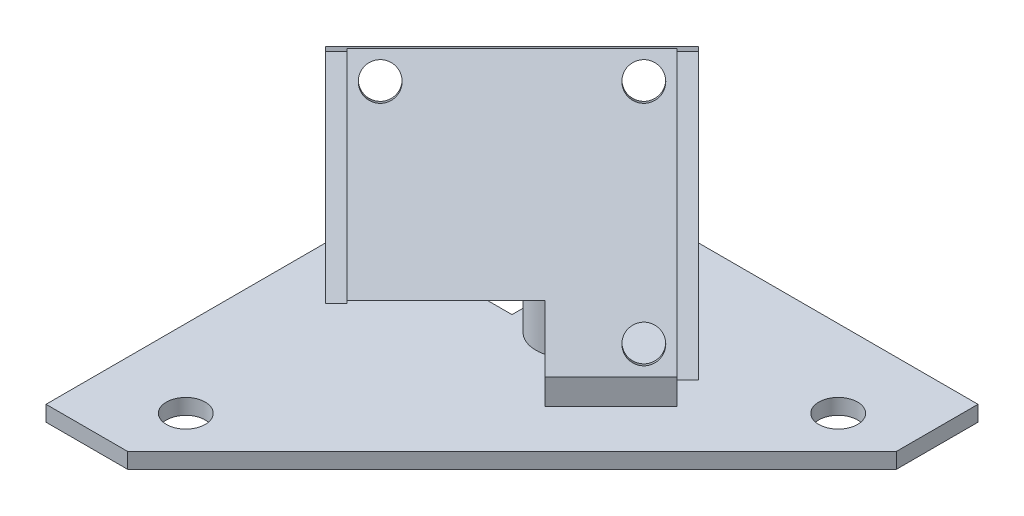
SolidWorks part; units mm, degrees
ref_plane "Front" through (0, 0, 0) normal (0, 0, 1) x (1, 0, 0)
ref_plane "Top" through (0, 0, 0) normal (0, 1, 0) x (1, 0, 0)
ref_plane "Right" through (0, 0, 0) normal (1, 0, 0) x (0, 0, -1)
sketch "草图1" plane through (0, 0, 0) normal (0, 1, 0) x (1, 0, 0)
  line L0 (87.1745, 16.672) -> (1.4976, -69.0049)
  line L1 (0, 0) -> (60, 0)
  line L2 (0, 0) -> (0, -60)
  line L3 (0, -60) -> (60, -60)
  line L4 (60, 0) -> (60, -60)
  line L5 (0, 0) -> (20, 0)
  line L6 (0, 0) -> (0, -20)
  line L7 (0, -20) -> (20, -20)
  line L8 (20, 0) -> (20, -20)
  circle A0 centre (10, -52) radius 2.5
  circle A1 centre (52, -10) radius 2.5
  dimension "D5" = 5
  dimension "D8" = 5
  dimension "D1" = 60
  dimension "D2" = 60
  dimension "D3" = 20
  dimension "D4" = 20
  dimension "D6" = 10
  dimension "D7" = 8
  dimension "D9" = 10
  dimension "D10" = 8
  dimension "D11" = 35
extrude "凸台-拉伸1" add sketch "草图1" along normal blind 2 contours L1 L8 L7 L2 L3 L4 region at (25.5687, 0, 25.5687)
ref_plane "基准面1" through (23.1124, 18.8712, 23.1124) normal (0.6124, 0.5, 0.6124) x (-0.7071, 0, 0.7071)
sketch "草图2" plane through (23.1124, 18.8712, 23.1124) normal (0.6124, 0.5, 0.6124) x (-0.7071, 0, 0.7071)
  line L0 (20.7547, -10.214) -> (-21.3736, -10.214) construction
  line L1 (-15, 16.786) -> (15, 16.786)
  line L2 (-15, 16.786) -> (-15, -13.214)
  line L3 (-15, -13.214) -> (15, -13.214)
  line L4 (15, 16.786) -> (15, -13.214)
  line L5 (-15, 16.786) -> (15, -13.214) construction
  line L6 (-15, -13.214) -> (15, 16.786) construction
  line L7 (0, -2.8326) -> (0, 36.0846) construction
  line L8 (27.4605, 1.786) -> (-33.4746, 1.786) construction
  line L10 (15, 16.786) -> (-3, 16.786)
  line L11 (15, 16.786) -> (15, 9.786)
  line L12 (15, 9.786) -> (-3, 9.786)
  line L13 (-3, 16.786) -> (-3, 9.786)
  circle A0 centre (12, -10.214) radius 2
  circle A1 centre (-12, -10.214) radius 2
  circle A2 centre (-12, 13.786) radius 2
  circle A3 centre (12, 13.786) radius 2
  point P0 (0, 1.786)
  dimension "D4" = 4
  dimension "D1" = 30
  dimension "D2" = 30
  dimension "D3" = 12
  dimension "D5" = 12
  dimension "D6" = 7
  dimension "D7" = 18
extrude "凸台-拉伸3" add sketch "草图2" along normal blind 2 separate body contours L13 L1 L2 L3 L4 L12 A2 A0 A1 region at (23.7017, 18.8514, 22.5393)
sketch "草图4" plane through (0, 2, 0) normal (0, 1, 0) x (1, 0, 0)
  line L12 (28.6936, -38.5931) -> (31.1685, -41.0679)
  line L13 (15.9657, -51.321) -> (28.6936, -38.5931)
  line L14 (-6.3082, -29.0471) -> (15.9657, -51.321)
  line L15 (29.0471, 6.3082) -> (-6.3082, -29.0471)
  line L16 (53.7959, -18.4405) -> (29.0471, 6.3082)
  line L17 (31.1685, -41.0679) -> (53.7959, -18.4405)
  line L18 (28.6936, -38.5931) -> (31.1685, -41.0679)
  line L19 (15.9657, -51.321) -> (28.6936, -38.5931)
  line L20 (-6.3082, -29.0471) -> (15.9657, -51.321)
  line L21 (29.0471, 6.3082) -> (-6.3082, -29.0471)
  line L22 (53.7959, -18.4405) -> (29.0471, 6.3082)
  line L23 (31.1685, -41.0679) -> (53.7959, -18.4405)
  circle A0 centre (25.5116, -18.4405) radius 4
  dimension "D2" = 8
  dimension "D3" = 15
  dimension "D4" = 20
  dimension "D1" = 10
extrude "凸台-拉伸4" add sketch "草图4" along normal up to surface (14.7556 mm away) contours A0 region at (25.5116, 2, 18.4405) up to face at (37.886, 6.9321, 18.087)
sketch "草图5" plane through (0, 2, 0) normal (0, 1, 0) x (1, 0, 0)
  line L4 (39.6537, -18.4405) -> (31.1685, -26.9258)
  line L5 (40.8785, -19.6653) -> (39.6537, -18.4405)
  line L6 (32.3932, -28.1506) -> (40.8785, -19.6653)
  line L7 (60, 0) -> (20, 0)
  line L8 (20, 0) -> (20, -20)
  line L9 (20, -20) -> (0, -20)
  line L10 (0, -20) -> (0, -60)
  line L11 (0, -60) -> (10.5025, -60)
  line L12 (10.5025, -60) -> (60, -10.5025)
  line L13 (60, -10.5025) -> (60, 0)
  line L14 (60, 0) -> (20, 0)
  line L15 (20, 0) -> (20, -20)
  line L16 (20, -20) -> (0, -20)
  line L17 (0, -20) -> (0, -60)
  line L18 (0, -60) -> (10.5025, -60)
  line L19 (10.5025, -60) -> (60, -10.5025)
  line L20 (60, -10.5025) -> (60, 0)
  line L21 (31.1685, -26.9258) -> (32.3932, -28.1506)
  line L22 (39.6537, -18.4405) -> (31.1685, -26.9258)
  line L23 (40.8785, -19.6653) -> (39.6537, -18.4405)
  line L24 (32.3932, -28.1506) -> (40.8785, -19.6653)
  line L25 (31.1685, -26.9258) -> (32.3932, -28.1506)
  dimension "D1" = 0
  dimension "D2" = 0
extrude "凸台-拉伸5" add sketch "草图5" along normal up to next contours L22 L25 L24 L23 region at (36.0235, 2, 23.2955)
sketch "草图6" plane through (24.3371, 19.8712, 24.3371) normal (0.6124, 0.5, 0.6124) x (0.4743, 0.3873, -0.7906)
  line L0 (-7.5069, 18.5271) -> (-17.7929, -2.0447)
  line L1 (-7.5069, 18.5271) -> (-9.2958, 19.4216)
  line L2 (-17.7929, -2.0447) -> (-19.5817, -1.1503)
  line L3 (-9.2958, 19.4216) -> (-19.5817, -1.1503)
  line L4 (19.3259, 5.1107) -> (5.9095, -21.7221)
  line L5 (19.3259, 5.1107) -> (21.1147, 4.2163)
  line L6 (5.9095, -21.7221) -> (7.6983, -22.6165)
  line L7 (21.1147, 4.2163) -> (7.6983, -22.6165)
  dimension "D1" = 2
  dimension "D2" = 2
extrude "凸台-拉伸6" add sketch "草图6" against normal up to surface (2 mm away) and the other way blind 3 up to face at (28.34, 14.7263, 21.269)
